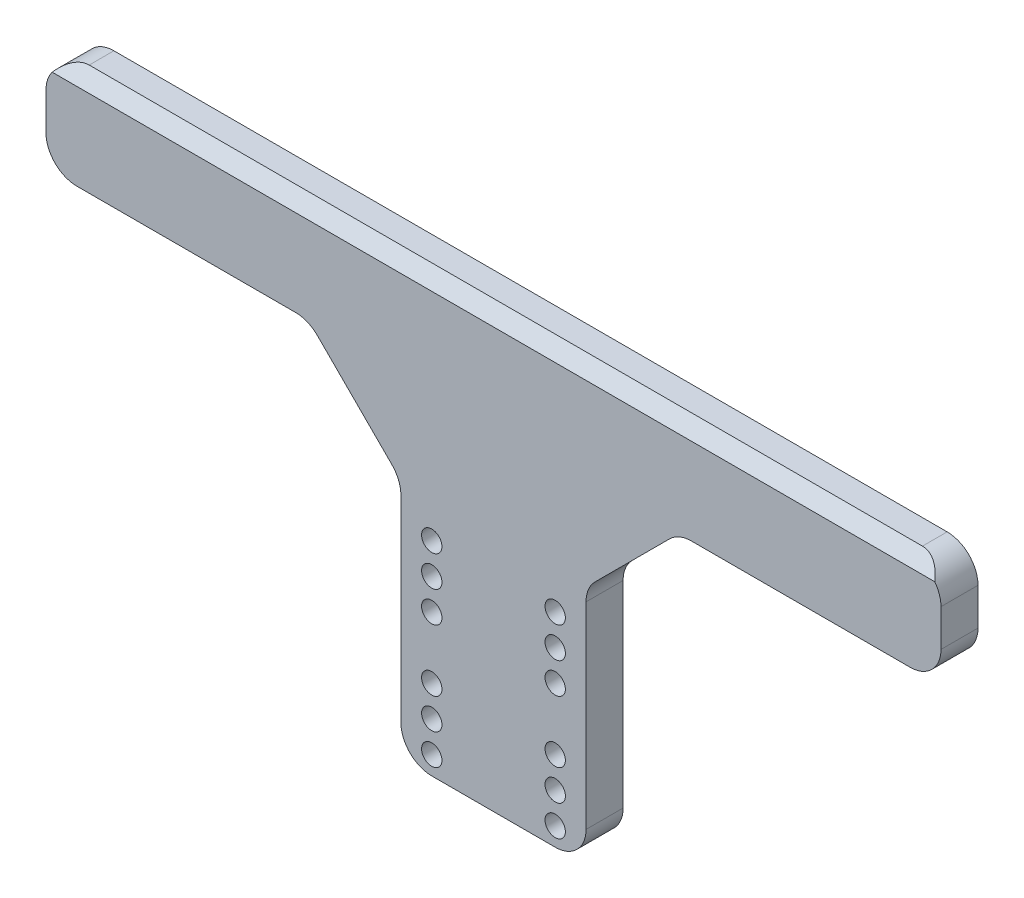
SolidWorks part; units mm, degrees
ref_plane "Front" through (0, 0, 0) normal (0, 0, 1) x (1, 0, 0)
ref_plane "Top" through (0, 0, 0) normal (0, 1, 0) x (1, 0, 0)
ref_plane "Right" through (0, 0, 0) normal (1, 0, 0) x (0, 0, -1)
sketch "Esquisse1" plane through (0, 0, 0) normal (0, 0, 1) x (1, 0, 0)
  line L1 (0, 0) -> (145, 0)
  line L2 (0, 0) -> (0, 40)
  line L3 (0, 40) -> (145, 40)
  line L4 (145, 0) -> (145, 40)
  dimension "D1" = 145
  dimension "D2" = 40
extrude "Boss.-Extru.1" add sketch "Esquisse1" along normal blind 6
sketch "Esquisse2" plane through (0, 0, 6) normal (0, 0, 1) x (1, 0, 0)
  line L0 (72.5, 0) -> (72.5, 40) construction
  line L1 (0, 0) -> (145, 0) construction
  line L2 (145, 40) -> (0, 40) construction
  line L3 (72.5, 13) -> (26.2893, 13) construction
  line L4 (62.5, 3) -> (62.5, 8) construction
  circle A0 centre (62.5, 23) radius 1.65
  circle A1 centre (62.5, 3) radius 1.65
  circle A2 centre (82.5, 3) radius 1.65
  circle A3 centre (82.5, 23) radius 1.65
  circle A4 centre (62.5, 28) radius 1.65
  circle A5 centre (62.5, 8) radius 1.65
  circle A6 centre (82.5, 8) radius 1.65
  circle A7 centre (82.5, 28) radius 1.65
  circle A8 centre (62.5, 33) radius 1.65
  circle A9 centre (62.5, 13) radius 1.65
  circle A10 centre (82.5, 13) radius 1.65
  circle A11 centre (82.5, 33) radius 1.65
  dimension "D1" = 20
  dimension "D2" = 20
  dimension "D3" = 3.3
  dimension "D4" = 3
  dimension "D6" = 5
  dimension "D5" = 3
extrude "Enlèv. mat.-Extru.1" cut sketch "Esquisse2" against normal through all both and the other way through all
sketch "Esquisse3" plane through (0, 0, 6) normal (0, 0, 1) x (1, 0, 0)
  line L0 (145, 0) -> (145, 40) construction
  line L1 (0, 40) -> (145, 40)
  line L2 (0, 40) -> (0, 70)
  line L3 (0, 70) -> (145, 70)
  line L4 (145, 40) -> (145, 70)
  dimension "D1" = 30
extrude "Boss.-Extru.2" add sketch "Esquisse3" against normal up to vertex (6 mm away) up to point (145, 40, 0)
chamfer "Chanfrein1" distance 2 angle 45 1 edges at (72.5, 70, 6)
sketch "Esquisse4" plane through (0, 0, 6) normal (0, 0, 1) x (1, 0, 0)
  line L0 (72.5, 0) -> (72.5, 70) construction
  line L1 (0, 0) -> (57.5, 0)
  line L2 (0, 0) -> (0, 54)
  line L3 (0, 54) -> (57.5, 54)
  line L4 (57.5, 0) -> (57.5, 54)
  line L5 (0, 0) -> (145, 0) construction
  line L6 (0, 70) -> (145, 70) construction
  line L7 (87.5, 0) -> (87.5, 54)
  line L8 (145, 54) -> (87.5, 54)
  line L9 (145, 0) -> (145, 54)
  line L10 (145, 0) -> (87.5, 0)
  dimension "D1" = 30
  dimension "D2" = 16
extrude "Enlèv. mat.-Extru.2" cut sketch "Esquisse4" against normal through all both and the other way through all
chamfer "Chanfrein2" distance 15 angle 45 2 edges at (87.5, 54, 3) (57.5, 54, 3)
fillet "Congé2" radius 5 10 edges at (145, 70, 2) (145, 54, 3) (102.5, 54, 3) (87.5, 39, 3) (87.5, 0, 3) (57.5, 0, 3) (57.5, 39, 3) (42.5, 54, 3) (0, 54, 3) (0, 70, 2)
